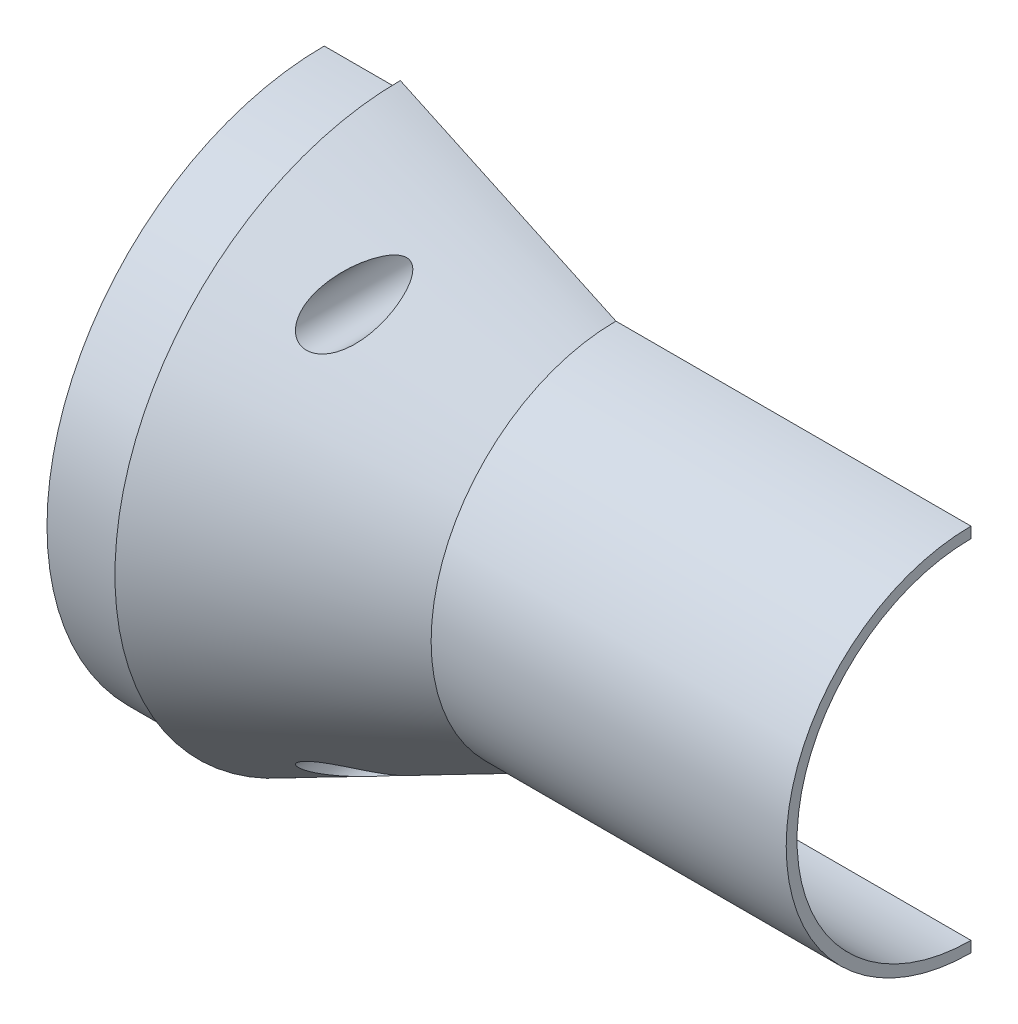
SolidWorks part; units mm, degrees
ref_plane "Спереди" through (0, 0, 0) normal (0, 0, 1) x (1, 0, 0)
ref_plane "Сверху" through (0, 0, 0) normal (0, 1, 0) x (1, 0, 0)
ref_plane "Справа" through (0, 0, 0) normal (1, 0, 0) x (0, 0, -1)
other "Configuration Table"
sketch "Эскиз1" plane through (0, 0, 0) normal (0, 0, 1) x (1, 0, 0)
  line L0 (0, 0) -> (190.9824, 0) construction
  line L1 (0, 35) -> (0, 51)
  line L8 (14, 48.5) -> (10, 48.5)
  line L11 (0, 35) -> (7, 35)
  line L12 (7, 35) -> (7, 32)
  line L13 (7, 32) -> (10, 32)
  line L14 (10, 32) -> (10, 48.5)
  line L15 (0, 51) -> (14, 51)
  line L16 (14, 51) -> (14, 52.5)
  line L17 (14, 52.5) -> (53.6734, 34)
  line L18 (53.6734, 34) -> (119, 34)
  line L19 (119, 34) -> (119, 32)
  line L20 (119, 32) -> (53.6734, 32)
  line L22 (14, 48.5) -> (53.6734, 32)
  line L23 (25, 43.9251) -> (25, 32)
  line L24 (25, 32) -> (35, 32)
  line L25 (35, 32) -> (35, 39.7662)
  line L26 (25, 43.9251) -> (35, 39.7662)
  circle A0 centre (30, 37) radius 3
  circle A1 centre (30, 37) radius 4.4741
  dimension "D16" = 6
  dimension "D1" = 70
  dimension "D2" = 64
  dimension "D3" = 105
  dimension "D4" = 97
  dimension "D5" = 7
  dimension "D6" = 3
  dimension "D7" = 4
  dimension "D8" = 102
  dimension "D9" = 25
  dimension "D10" = 64
  dimension "D11" = 109
  dimension "D12" = 2
  dimension "D13" = 10
  dimension "D14" = 15
  dimension "D15" = 0
  dimension "D17" = 5
  dimension "D18" = 5
revolve "Повернуть2" add sketch "Эскиз1" angle 180 about L0 region at (37.4215, 39.833, 0)
extrude "Бобышка-Вытянуть3" add sketch "Эскиз1<11>" along normal up to body contours L23 L24 L25 L26
sketch "Эскиз1<11>" plane through (0, 0, 0) normal (0, 0, 1) x (1, 0, 0) same geometry as "Эскиз1"
extrude "Вырез-Вытянуть3" cut sketch "Эскиз1<12>" along normal blind 204.9 contours A1
sketch "Эскиз1<12>" plane through (0, 0, 0) normal (0, 0, 1) x (1, 0, 0) same geometry as "Эскиз1"
extrude "Бобышка-Вытянуть4" add sketch "Эскиз1<14>" along normal blind 10 contours A1
sketch "Эскиз1<14>" plane through (0, 0, 0) normal (0, 0, 1) x (1, 0, 0) same geometry as "Эскиз1"
extrude "Вырез-Вытянуть4" cut sketch "Эскиз1<16>" along normal blind 32 contours A0
sketch "Эскиз1<16>" plane through (0, 0, 0) normal (0, 0, 1) x (1, 0, 0) same geometry as "Эскиз1"
mirror "Зеркальное отражение1" about plane through (0, 0, 0) normal (0, 1, 0) of "Вырез-Вытянуть4", "Бобышка-Вытянуть4", "Вырез-Вытянуть3", "Бобышка-Вытянуть3"
